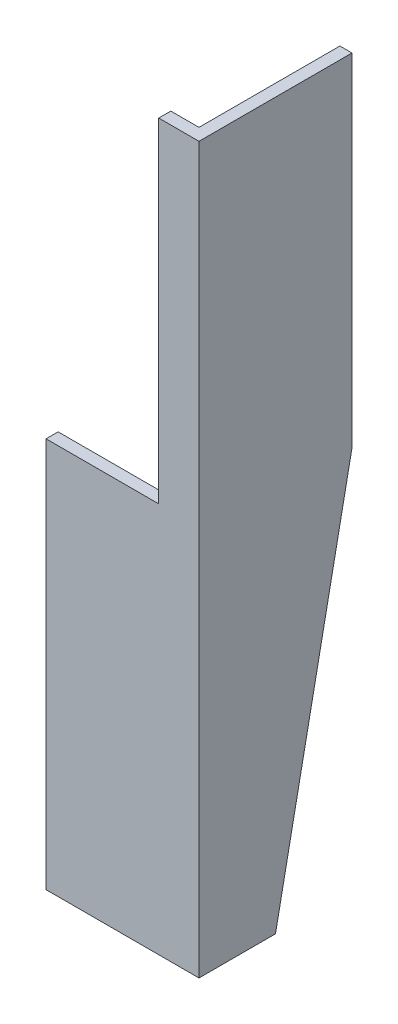
SolidWorks part; units mm, degrees
ref_plane "Alzado" through (0, 0, 0) normal (0, 0, 1) x (1, 0, 0)
ref_plane "Planta" through (0, 0, 0) normal (0, 1, 0) x (1, 0, 0)
ref_plane "Vista lateral" through (0, 0, 0) normal (1, 0, 0) x (0, 0, -1)
sketch "Croquis1" plane through (0, 0, 0) normal (0, 1, 0) x (1, 0, 0)
  line L0 (0, 0) -> (-38, 0)
  line L1 (0, 0) -> (0, 38)
  line L2 (-3, 3) -> (-3, 38)
  line L3 (-3, 3) -> (-38, 3)
  line L4 (-3, 38) -> (0, 38)
  line L5 (-38, 3) -> (-38, 0)
  dimension "D1" = 38
  dimension "D2" = 3
extrude "Saliente-Extruir1" add sketch "Croquis1" along normal blind 180
sketch "Croquis2" plane through (0, 0, 0) normal (1, 0, 0) x (0, 0, -1)
  line L0 (0, 95) -> (38, 95) construction
  line L1 (0, 180) -> (0, 0) construction
  line L2 (38, 180) -> (38, 0) construction
  line L3 (38, 180) -> (3, 180) construction
  line L4 (38, 95) -> (19, 0)
  line L5 (0, 0) -> (38, 0) construction
  line L6 (19, 0) -> (38, 0)
  line L7 (38, 0) -> (38, 95)
  dimension "D1" = 85
extrude "Cortar-Extruir1" cut sketch "Croquis2" against normal up to surface (3 mm away) up to face at (-3, 90, -20.5)
sketch "Croquis3" plane through (0, 0, 0) normal (0, 0, 1) x (1, 0, 0)
  line L0 (0, 180) -> (0, 0) construction
  line L1 (-38, 180) -> (-10, 180)
  line L2 (-38, 180) -> (-38, 97)
  line L3 (-38, 97) -> (-10, 97)
  line L4 (-10, 180) -> (-10, 97)
  dimension "D1" = 83
  dimension "D2" = 10
extrude "Cortar-Extruir2" cut sketch "Croquis3" against normal up to surface (3 mm away) up to face at (-20.5, 90, -3)
